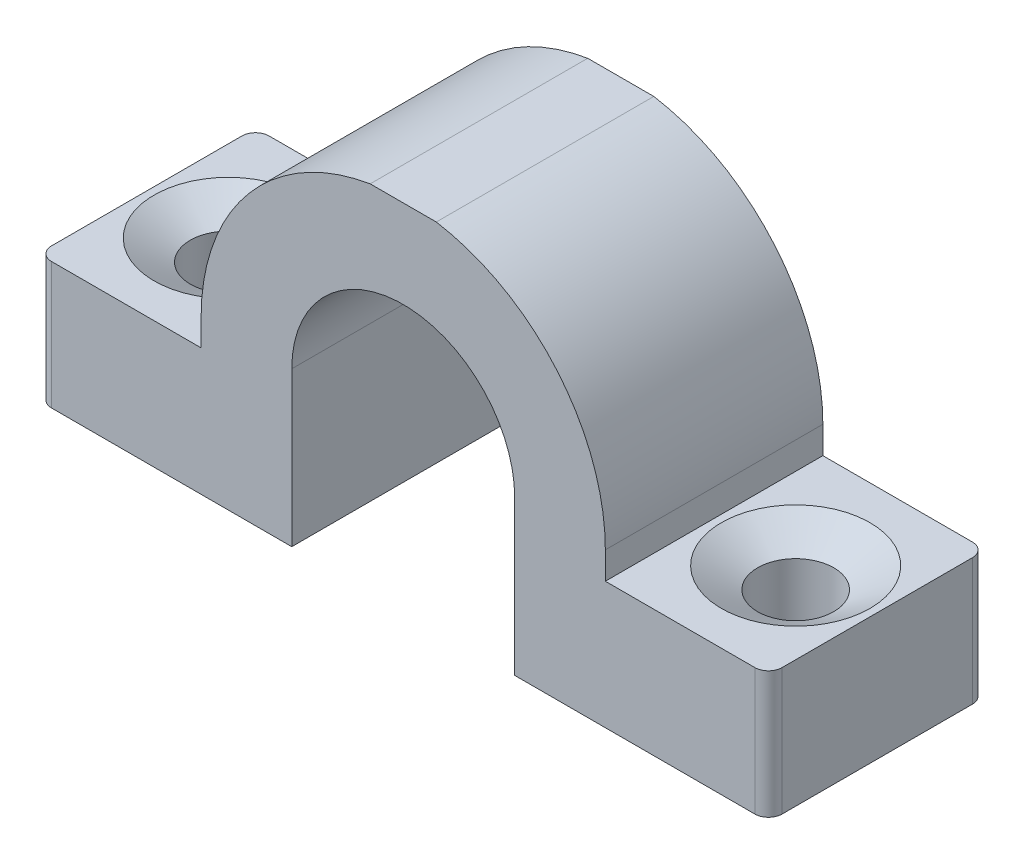
SolidWorks part; units mm, degrees
ref_plane "Front Plane" through (0, 0, 0) normal (0, 0, 1) x (1, 0, 0)
ref_plane "Top Plane" through (0, 0, 0) normal (0, 1, 0) x (1, 0, 0)
ref_plane "Right Plane" through (0, 0, 0) normal (1, 0, 0) x (0, 0, -1)
sketch "Sketch1" plane through (0, 0, 0) normal (0, 0, 1) x (1, 0, 0)
  line L0 (-11.15, 0) -> (-11.15, -1.5)
  line L1 (-11.15, -1.5) -> (-20.15, -1.5)
  line L2 (-20.15, -1.5) -> (-20.15, -8.5)
  line L3 (-20.15, -8.5) -> (-6.15, -8.5)
  line L4 (-6.15, -8.5) -> (-6.15, 0)
  line L5 (6.15, 0) -> (6.15, -8.5)
  line L6 (6.15, -8.5) -> (20.15, -8.5)
  line L7 (20.15, -8.5) -> (20.15, -1.5)
  line L8 (20.15, -1.5) -> (11.15, -1.5)
  line L9 (11.15, -1.5) -> (11.15, 0)
  arc A0 (6.15, 0) -> (-6.15, 0) centre (0, 0) ccw
  arc A1 (11.15, 0) -> (-11.15, 0) centre (0, 0) ccw
  dimension "D1" = 12.3
  dimension "D2" = 5
  dimension "D3" = 7
  dimension "D4" = 14
  dimension "D5" = 8.5
extrude "Boss-Extrude1" add sketch "Sketch1" along normal blind 12
sketch "Sketch4" plane through (0, -1.5, 0) normal (0, 1, 0) x (1, 0, 0)
  line L0 (-11.15, 0) -> (-20.15, 0) construction
  line L1 (-20.15, -12) -> (-20.15, 0) construction
  line L2 (20.15, 0) -> (11.15, 0) construction
  line L3 (20.15, -12) -> (20.15, 0) construction
  circle A0 centre (-15.65, -6) radius 2.1
  circle A1 centre (15.65, -6) radius 2.1
  point P4 (-15.65, 0)
  point P7 (-20.15, -6)
  point P12 (15.65, 0)
  point P15 (20.15, -6)
  dimension "D1" = 4.2
extrude "Cut-Extrude1" cut sketch "Sketch4" against normal through all
chamfer "Chamfer1" distance 2 angle 30 2 edges at (13.55, -1.5, 6) (-17.75, -1.5, 6) first distance on face at (13.55, -1.5, 6) first distance on face at (-17.75, -1.5, 6)
ref_plane "Plane1" through (0, 11, 0) normal (0, 1, 0) x (1, 0, 0)
sketch "Sketch5" plane through (0, 11, 0) normal (0, 1, 0) x (1, 0, 0)
  line L1 (-8.3673, 1.4476) -> (8.7588, 1.4476)
  line L2 (-8.3673, 1.4476) -> (-8.3673, -13.0362)
  line L3 (-8.3673, -13.0362) -> (8.7588, -13.0362)
  line L4 (8.7588, 1.4476) -> (8.7588, -13.0362)
  line L5 (-8.3673, 1.4476) -> (8.7588, -13.0362) construction
  line L6 (-8.3673, -13.0362) -> (8.7588, 1.4476) construction
  point P0 (0.1957, -5.7943)
extrude "Cut-Extrude2" cut sketch "Sketch5" along normal through all
fillet "Fillet2" radius 0.75 4 edges at (20.15, -5, 0) (20.15, -5, 12) (-20.15, -5, 0) (-20.15, -5, 12)
